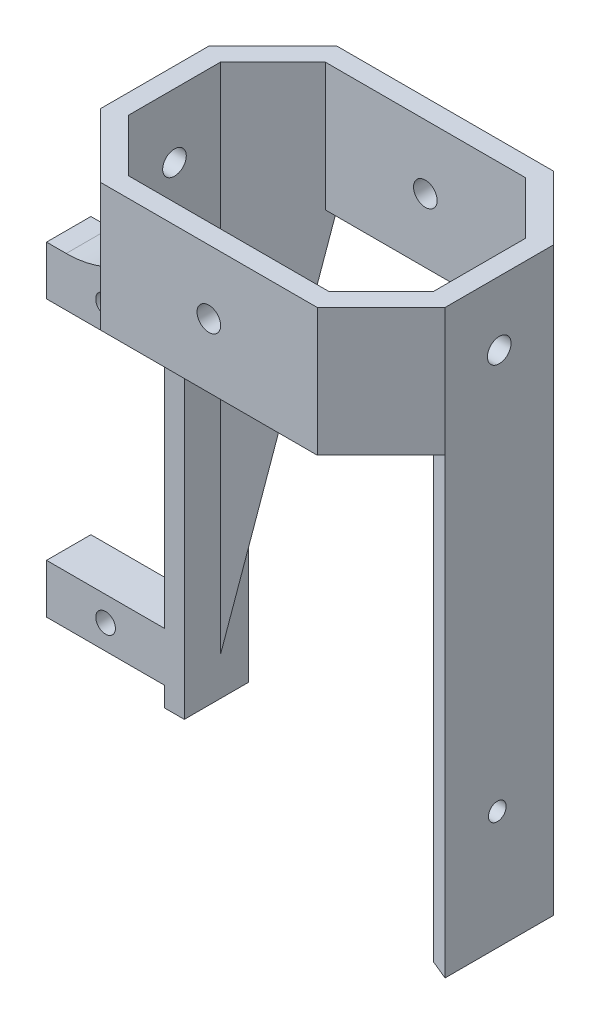
SolidWorks part; units mm, degrees
ref_plane "Front Plane" through (0, 0, 0) normal (0, 0, 1) x (1, 0, 0)
ref_plane "Top Plane" through (0, 0, 0) normal (0, 1, 0) x (1, 0, 0)
ref_plane "Right Plane" through (0, 0, 0) normal (1, 0, 0) x (0, 0, -1)
sketch "Sketch1" plane through (0, 0, 0) normal (0, 1, 0) x (1, 0, 0)
  line L7 (0, 0) -> (20.3603, 0)
  line L8 (20.3603, 0) -> (25.6801, -5.3199)
  line L9 (25.6801, -5.3199) -> (25.6801, -14.6801)
  line L10 (25.6801, -14.6801) -> (20.3603, -20)
  line L11 (20.3603, -20) -> (0, -20)
  line L12 (0, -20) -> (-5.3199, -14.6801)
  line L13 (-5.3199, -14.6801) -> (-5.3199, -5.3199)
  line L14 (-5.3199, -5.3199) -> (0, 0)
  line L15 (-7.3199, -4.4914) -> (-0.8284, 2)
  line L16 (-0.8284, 2) -> (21.1887, 2)
  line L17 (21.1887, 2) -> (27.6801, -4.4914)
  line L18 (27.6801, -4.4914) -> (27.6801, -15.5086)
  line L19 (27.6801, -15.5086) -> (21.1887, -22)
  line L20 (21.1887, -22) -> (-0.8284, -22)
  line L21 (-0.8284, -22) -> (-7.3199, -15.5086)
  line L22 (-7.3199, -15.5086) -> (-7.3199, -4.4914)
  point P2 (0, 0)
  point P7 (0, 0)
  dimension "D1" = 20
  dimension "D2" = 31
  dimension "D4" = 9.3603
  dimension "D5" = 7.5234
  dimension "D6" = 7.5234
  dimension "D7" = 7.5234
  dimension "D3" = 2
extrude "Boss-Extrude1" add sketch "Sketch1" along normal blind 13
sketch "Sketch7" plane through (0, 0, 0) normal (0, -1, 0) x (1, 0, 0)
  line L1 (25.6801, 14.6801) -> (25.6801, 12.6962)
  line L2 (25.6801, 14.6801) -> (25.6801, 5.3199) construction
  line L3 (25.6801, 12.6962) -> (25.6801, 5.3199)
  line L4 (25.6801, 5.3199) -> (25.6801, 7.3038)
  line L5 (27.6801, 15.5086) -> (27.6801, 4.4914) construction
  line L6 (27.6801, 7.3038) -> (27.6801, 12.6962)
  arc A0 (25.6801, 7.3038) -> (27.6801, 7.3038) centre (26.6801, 7.3038) ccw
  arc A1 (27.6801, 12.6962) -> (25.6801, 12.6962) centre (26.6801, 12.6962) ccw
  point P14 (0, 0)
  line M6 (27.6801, 4.4914) -> (27.6801, 15.5086)
  line M16 (25.6801, 14.6801) -> (25.6801, 5.3199)
extrude "Boss-Extrude2" add sketch "Sketch7" along normal blind 46 contours A1 A0 M6 M16 region at (26.6801, 0, 10)
sketch "Sketch8" plane through (27.6801, 0, 0) normal (1, 0, 0) x (0, 0, -1)
  line L0 (-15.5086, 13) -> (-4.4914, 13) construction
  line L1 (-12.6962, -46) -> (-12.6962, 0) construction
  circle A0 centre (-10.1962, -34) radius 0.9
  point P6 (0, 0)
  dimension "D3" = 1.8
  dimension "D1" = 47
  dimension "D2" = 2.5
extrude "Cut-Extrude1" cut sketch "Sketch8" against normal blind 10
sketch "Sketch9" plane through (0, 0, 22) normal (0, 0, 1) x (1, 0, 0)
  line L0 (-0.8284, 13) -> (21.1887, 13) construction
  line L1 (-0.8284, 13) -> (-0.8284, 0) construction
  circle A0 centre (10.1716, 6.5) radius 1.2
  dimension "D1" = 6.5
  dimension "D2" = 11
extrude "Cut-Extrude2" cut sketch "Sketch9" against normal blind 40
sketch "Sketch10" plane through (27.6801, 0, 0) normal (1, 0, 0) x (0, 0, -1)
  line L0 (-15.5086, 13) -> (-4.4914, 13) construction
  circle A0 centre (-10, 6.5) radius 1.2
  point P4 (-10, 13)
  dimension "D1" = 6.5
extrude "Cut-Extrude3" cut sketch "Sketch10" against normal blind 50
sketch "Sketch11" plane through (0, 0, 0) normal (0, -1, 0) x (1, 0, 0)
  line L0 (-5.3199, 9) -> (-7.3199, 9)
  line L3 (-7.3199, 9) -> (-7.3199, 4.4914)
  line L4 (-7.3199, 4.4914) -> (-5.3199, 2.4914)
  line L5 (-0.8284, -2) -> (-7.3199, 4.4914) construction
  line L6 (-5.3199, 2.4914) -> (-5.3199, 9)
  point P2 (0, 0)
  point P4 (0, 0)
  point P6 (0, 0)
  point P12 (0, 0)
  point P13 (0, 0)
  point P14 (0, 0)
  point P15 (-7.3199, 10)
  point P16 (0, 0)
  point P17 (-5.3199, 10)
  point P18 (-7.3199, 10)
extrude "Boss-Extrude3" add sketch "Sketch11" along normal blind 43
sketch "Sketch12" plane through (-7.3199, 0, 0) normal (-1, 0, 0) x (0, 0, 1)
  line L0 (9, -8) -> (4.4914, -8)
  line L1 (9, -43) -> (9, 0) construction
  line L2 (4.4914, 13) -> (4.4914, -43) construction
  line L3 (4.4914, -8) -> (4.4914, -13)
  line L4 (4.4914, -13) -> (9, -13)
  line L5 (9, -13) -> (9, -8)
  line L6 (4.4914, -36) -> (9, -36)
  line L7 (4.4914, -36) -> (4.4914, -41)
  line L8 (4.4914, -41) -> (9, -41)
  line L9 (9, -41) -> (9, -36)
  dimension "D1" = 8
  dimension "D2" = 5
  dimension "D3" = 23
  dimension "D4" = 5
extrude "Boss-Extrude4" add sketch "Sketch12" along normal blind 12
sketch "Sketch13" plane through (0, 0, 9) normal (0, 0, 1) x (1, 0, 0)
sketch "Sketch14" plane through (0, 0, 9) normal (0, 0, 1) x (1, 0, 0)
  line L0 (-19.3199, -8) -> (-7.3199, -8) construction
  line L1 (-19.3199, -36) -> (-7.3199, -36) construction
  circle A0 centre (-13.3199, -10.5) radius 1
  circle A1 centre (-13.3199, -38.5) radius 1
  dimension "D1" = 2.5
  dimension "D2" = 2.5
  dimension "D3" = 2
  dimension "D4" = 2
extrude "Cut-Extrude4" cut sketch "Sketch14" against normal blind 30
sketch "Sketch17" plane through (-1.4142, 0, -1.4142) normal (-0.7071, 0, -0.7071) x (-0.7071, 0, 0.7071)
  line L0 (-0.8284, 0) -> (8.3519, -43)
  line L1 (8.3519, -43) -> (8.3519, 0)
  line L2 (8.3519, 13) -> (8.3519, -8) construction
  line L3 (8.3519, 0) -> (-0.8284, 0)
extrude "Boss-Extrude5" add sketch "Sketch17" against normal up to surface (2 mm away) up to face at (-2.6599, 6.5, 2.6599)
fillet "Fillet3" radius 10 1 edges at (-7.3199, -8, 6.7457)
sketch "Sketch18" plane through (0, 0, 0) normal (0, -1, 0) x (1, 0, 0)
  line L0 (27.6801, 15.5086) -> (25.6801, 14.6801)
  line L1 (25.6801, 14.6801) -> (25.6801, 5.3199)
  line L2 (25.6801, 5.3199) -> (27.6801, 4.4914)
  line L3 (27.6801, 4.4914) -> (27.6801, 15.5086)
extrude "Boss-Extrude6" add sketch "Sketch18" along normal blind 46
extrude "Cut-Extrude5" cut sketch "Sketch8<2>" against normal blind 30
sketch "Sketch8<2>" plane through (27.6801, 0, 0) normal (1, 0, 0) x (0, 0, -1) same geometry as "Sketch8"
